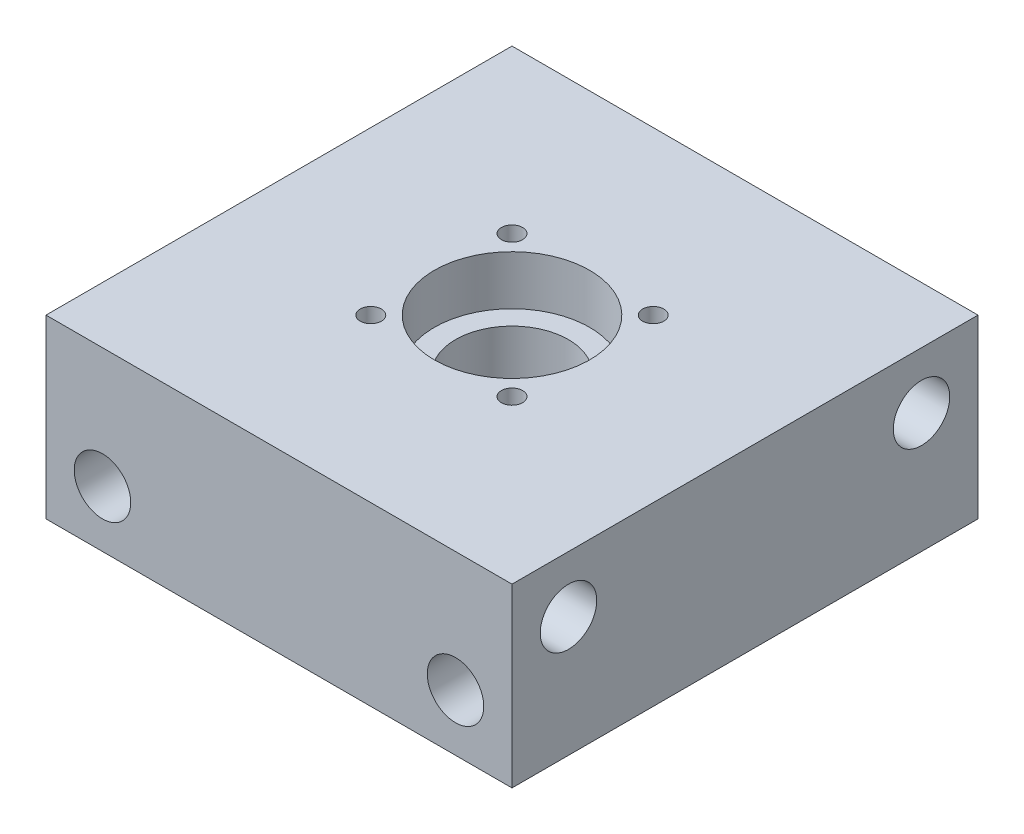
SolidWorks part; units mm, degrees
material "ABS"
ref_plane "Front Plane" through (0, 0, 0) normal (0, 0, 1) x (1, 0, 0)
ref_plane "Top Plane" through (0, 0, 0) normal (0, 1, 0) x (1, 0, 0)
ref_plane "Right Plane" through (0, 0, 0) normal (1, 0, 0) x (0, 0, -1)
sketch "Sketch1" plane through (0, 0, 0) normal (0, 1, 0) x (1, 0, 0)
  line L0 (-25, 94.322) -> (-25, -161.1056) construction
  line L1 (0, 212.1837) -> (0, -209.6879) construction
  line L2 (-178.557, 25) -> (189.3494, 25) construction
  line L3 (-284.8586, 0) -> (271.277, 0) construction
  line L4 (-33, 29) -> (33, 29)
  line L5 (-29, 33) -> (-21, 33)
  line L6 (-29, 33) -> (-29, -33)
  line L7 (-29, -33) -> (-21, -33)
  line L8 (-21, 33) -> (-21, -33)
  line L9 (-33, 21) -> (33, 21)
  line L10 (-33, -29) -> (-33, -21)
  line L11 (-178.557, -25) -> (189.3494, -25) construction
  line L12 (33, -29) -> (33, -21)
  line L13 (-33, 29) -> (33, 29)
  line L14 (-33, 29) -> (-33, 21)
  line L15 (-33, 21) -> (33, 21)
  line L16 (33, 29) -> (33, 21)
  line L17 (-33, -21) -> (33, -21)
  line L18 (-33, -29) -> (33, -29)
  line L19 (-33, -21) -> (33, -21)
  line L20 (-33, -29) -> (33, -29)
  line L21 (29, -33) -> (21, -33)
  line L22 (29, 33) -> (21, 33)
  line L23 (25, 94.322) -> (25, -161.1056) construction
  line L24 (21, 33) -> (21, -33)
  line L25 (29, 33) -> (29, -33)
  line L26 (13.2332, 10) -> (11.6166, 12.8)
  line L27 (-33, 33) -> (33, 33)
  line L28 (-33, 33) -> (-33, -33)
  line L29 (-33, -33) -> (33, -33)
  line L30 (33, 33) -> (33, -33)
  line L31 (-6.7668, 10) -> (-8.3834, 12.8)
  line L32 (-8.3834, 12.8) -> (-11.6166, 12.8)
  line L33 (-11.6166, 12.8) -> (-13.2332, 10)
  line L34 (-13.2332, 10) -> (-11.6166, 7.2)
  line L35 (-11.6166, 7.2) -> (-8.3834, 7.2)
  line L36 (-8.3834, 7.2) -> (-6.7668, 10)
  line L37 (11.6166, 12.8) -> (8.3834, 12.8)
  line L38 (8.3834, 12.8) -> (6.7668, 10)
  line L39 (6.7668, 10) -> (8.3834, 7.2)
  line L40 (8.3834, 7.2) -> (11.6166, 7.2)
  line L41 (11.6166, 7.2) -> (13.2332, 10)
  line L42 (13.2332, -10) -> (11.6166, -7.2)
  line L43 (11.6166, -7.2) -> (8.3834, -7.2)
  line L44 (8.3834, -7.2) -> (6.7668, -10)
  line L45 (6.7668, -10) -> (8.3834, -12.8)
  line L46 (8.3834, -12.8) -> (11.6166, -12.8)
  line L47 (11.6166, -12.8) -> (13.2332, -10)
  line L48 (-6.7668, -10) -> (-8.3834, -7.2)
  line L49 (-8.3834, -7.2) -> (-11.6166, -7.2)
  line L50 (-11.6166, -7.2) -> (-13.2332, -10)
  line L51 (-13.2332, -10) -> (-11.6166, -12.8)
  line L52 (-11.6166, -12.8) -> (-8.3834, -12.8)
  line L53 (-8.3834, -12.8) -> (-6.7668, -10)
  circle A0 centre (0, 0) radius 11
  circle A1 centre (0, 0) radius 8
  circle A2 centre (-10, 10) radius 1.5
  circle A3 centre (10, 10) radius 1.5
  circle A4 centre (10, 10) radius 2.8 construction
  circle A5 centre (10, -10) radius 1.5
  circle A6 centre (-10, 10) radius 2.8 construction
  circle A7 centre (10, -10) radius 2.8 construction
  circle A8 centre (-10, -10) radius 1.5
  circle A9 centre (-10, -10) radius 2.8 construction
  dimension "D5" = 2
  dimension "D6" = 2
  dimension "D7" = 3
  dimension "D14" = 5.6
  dimension "D2" = 25
  dimension "D3" = 25
  dimension "D4" = 4
  dimension "D8" = 10
  dimension "D9" = 10
  dimension "D12" = 8
  dimension "D13" = 4
extrude "Boss-Extrude1" add sketch "Sketch1" along normal blind 25 contours L24 L9 L8 L17 A3 A2 A0 | L24 L4 L8 L9 | L6 L9 L8 L4 | L27 L8 L4 L24 | L8 L5 L6 L4 | L27 L28 L4 L6 | L4 L14 L9 L6 | L9 L28 L17 L6 | L6 L17 L8 L9 | L6 L18 L8 L17 | L10 L18 L6 L17 | L28 L29 L6 L18 | L18 L6 L7 L8 | L24 L17 L8 L18 | L8 L29 L24 L18 | L25 L20 L24 L21 | L25 L19 L24 L20 | L17 L25 L18 L12 | L30 L18 L25 L29 | L25 L15 L24 L19 | L30 L9 L25 L17 | L25 L13 L24 L15 | L4 L25 L9 L16 | L25 L22 L24 L13 | L30 L27 L25 L4 | L35 L36 L31 L32 L33 L34 A2 | L40 L41 L26 L37 L38 L39 A3 | L46 L47 L42 L43 L44 L45 A5 | L52 L53 L48 L49 L50 L51 A8 region at (-31, 0, -31) region at (-31, 0, -25) region at (-25, 0, -31) region at (-25, 0, -25) region at (-31, 0, 0) region at (0, 0, -31) region at (0, 0, -25) region at (-25, 0, 0) region at (-31, 0, 25) region at (25, 0, -31) region at (25, 0, -25) region at (0, 0, -20.406) region at (-25, 0, 25) region at (-31, 0, 31) region at (31, 0, -31) region at (31, 0, -25) region at (25, 0, 0) region at (0, 0, 25) region at (-25, 0, 31) region at (31, 0, 0) region at (25, 0, 25) region at (0, 0, 31) region at (31, 0, 25) region at (25, 0, 31) region at (31, 0, 31) region at (12.3508, 0, -8.6428) region at (-7.6492, 0, -8.6428) region at (12.3508, 0, 11.3572) region at (-7.6492, 0, 11.3572)
extrude "Boss-Extrude2" add sketch "Sketch1<4>" along normal blind 18 contours A0 A1 region at (-10.6889, 0, 0)
sketch "Sketch1<4>" plane through (0, 0, 0) normal (0, 1, 0) x (1, 0, 0) same geometry as "Sketch1"
sketch "Sketch2" plane through (-33, 0, 0) normal (-1, 0, 0) x (0, 0, 1)
  line L0 (0, 0) -> (0, 25) construction
  line L1 (-33, 25) -> (33, 25) construction
  circle A0 centre (-25, 17) radius 4
  circle A1 centre (25, 17) radius 4
  dimension "D3" = 8
  dimension "D1" = 25
  dimension "D2" = 8
extrude "Cut-Extrude1" cut sketch "Sketch2" against normal through all
sketch "Sketch3" plane through (0, 0, -33) normal (0, 0, -1) x (-1, 0, 0)
  line L0 (0, 0) -> (0, 25) construction
  line L1 (33, 25) -> (-33, 25) construction
  line L2 (33, 0) -> (-33, 0) construction
  circle A0 centre (-25, 8) radius 4
  circle A1 centre (25, 8) radius 4
  dimension "D1" = 8
  dimension "D2" = 25
  dimension "D3" = 8
extrude "Cut-Extrude2" cut sketch "Sketch3" against normal through all
extrude "Cut-Extrude3" cut sketch "Sketch1<5>" along normal blind 2.5 contours L52 L53 L48 L49 L50 L51 A8 | L35 L36 L31 L32 L33 L34 A2 | L40 L41 L26 L37 L38 L39 A3 | L46 L47 L42 L43 L44 L45 A5 region at (12.3508, 0, -8.6428) region at (-7.6492, 0, -8.6428) region at (12.3508, 0, 11.3572) region at (-7.6492, 0, 11.3572)
sketch "Sketch1<5>" plane through (0, 0, 0) normal (0, 1, 0) x (1, 0, 0) same geometry as "Sketch1"
equation "\"rod_diameter\"= 8"
equation "\"rod_hole_thickness\"= 4"
equation "\"rod_radius\"= \"rod_diameter\" / 2"
equation "\"platter_diameter\"= 320"
equation "\"platter_radius\"= \"platter_diameter\" / 2"
equation "\"extruder_mount_hole_spacing\"= 50"
equation "\"arm_rod_spacing\"= 40"
equation "\"top_frame_rod_spacing\"= \"arm_rod_spacing\" + 40"
equation "\"motor_level_rod_spacing\"= 15"
equation "\"linear_bearing_diameter\"= 15"
equation "\"z_rod_spacing\"= 75"
equation "\"platter_rod_spacing\"= 50"
equation "\"rod_nut_thickness\"= 6.5"
equation "\"rod_nut_inscribed_diameter\"= 13"
equation "\"D2@Sketch1\"=\"platter_rod_spacing\"/2"
equation "\"D3@Sketch1\"=\"platter_rod_spacing\"/2"
equation "\"D12@Sketch1\"=\"rod_diameter\""
equation "\"D4@Sketch1\"=\"rod_hole_thickness\""
equation "\"D13@Sketch1\"=\"rod_hole_thickness\""
equation "\"D1@Boss-Extrude1\"= \"rod_diameter\" * 2 + \"rod_hole_thickness\" * 2 + 1"
equation "\"D1@Boss-Extrude2\"= \"D1@Boss-Extrude1\" - 7"
equation "\"D1@Sketch2\"=\"platter_rod_spacing\"/2"
equation "\"D2@Sketch2\"=\"rod_radius\"+\"rod_hole_thickness\""
equation "\"D3@Sketch2\"=\"rod_diameter\""
equation "\"D1@Sketch3\"=\"rod_diameter\""
equation "\"D2@Sketch3\"=\"platter_rod_spacing\"/2"
equation "\"D3@Sketch3\"=\"rod_radius\"+\"rod_hole_thickness\""
